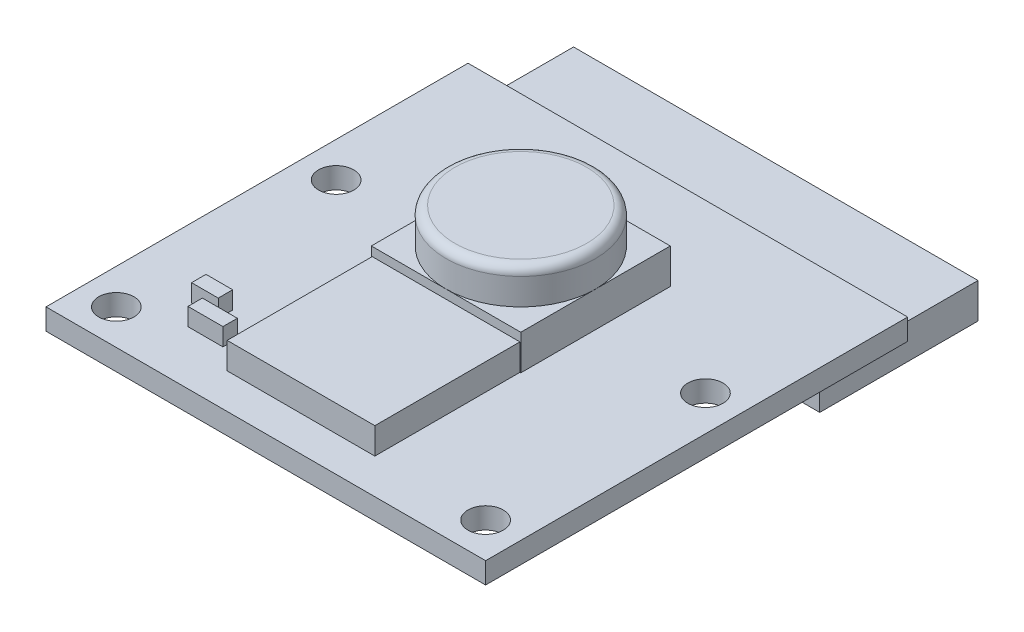
SolidWorks part; units mm, degrees
ref_plane "Front Plane" through (0, 0, 0) normal (0, 0, 1) x (1, 0, 0)
ref_plane "Top Plane" through (0, 0, 0) normal (0, 1, 0) x (1, 0, 0)
ref_plane "Right Plane" through (0, 0, 0) normal (1, 0, 0) x (0, 0, -1)
sketch "Sketch1" plane through (0, 0, 0) normal (0, 1, 0) x (1, 0, 0)
  line L0 (2, 22) -> (23, 22) construction
  line L1 (0, 24) -> (25, 24)
  line L2 (0, 24) -> (0, 0)
  line L3 (0, 0) -> (25, 0)
  line L4 (25, 24) -> (25, 0)
  line L5 (8.25, 18.75) -> (16.75, 18.75)
  line L6 (8.25, 18.75) -> (8.25, 10.25)
  line L8 (16.75, 18.75) -> (16.75, 10.25)
  line L9 (23, 22) -> (23, 14.5) construction
  line L10 (23, 2) -> (2, 2) construction
  line L11 (23, 14.5) -> (23, 2) construction
  line L12 (2, 2) -> (2, 14.5) construction
  line L13 (12.5, 14.5) -> (23, 14.5) construction
  line L14 (0, 24) -> (1, 29) construction
  line L17 (8.3, 2) -> (16.7, 2)
  line L19 (1, 29) -> (24, 29)
  line L20 (1, 29) -> (1, 20)
  line L21 (1, 20) -> (24, 20)
  line L22 (24, 29) -> (24, 20)
  line L23 (24, 29) -> (25, 24) construction
  line L24 (8.25, 10.25) -> (16.75, 10.25)
  line L25 (8.3, 2) -> (8.3, 10.25)
  line L26 (16.7, 2) -> (16.7, 10.25)
  line L27 (8.25, 10.25) -> (8.3, 2) construction
  line L28 (16.75, 10.25) -> (16.7, 2) construction
  line L30 (3.9479, 5.1506) -> (5.4647, 5.1506)
  line L31 (3.9479, 5.1506) -> (3.9479, 4.3307)
  line L32 (3.9479, 4.3307) -> (5.4647, 4.3307)
  line L33 (5.4647, 5.1506) -> (5.4647, 4.3307)
  line L34 (5.0137, 3.8797) -> (7.002, 3.8797)
  line L35 (5.0137, 3.8797) -> (5.0137, 3.0598)
  line L36 (5.0137, 3.0598) -> (7.002, 3.0598)
  line L37 (7.002, 3.8797) -> (7.002, 3.0598)
  circle A0 centre (2, 22) radius 1 construction
  circle A1 centre (2, 2) radius 1
  circle A2 centre (23, 22) radius 1 construction
  circle A3 centre (23, 2) radius 1
  circle A4 centre (2, 14.5) radius 1
  circle A5 centre (23, 14.5) radius 1
  circle A6 centre (12.5, 14.5) radius 4.25
  dimension "D1" = 2
  dimension "D8" = 14.5
  dimension "D10" = 8.5
  dimension "D2" = 25
  dimension "D3" = 24
  dimension "D4" = 20
  dimension "D5" = 21
  dimension "D6" = 2
  dimension "D7" = 2
  dimension "D9" = 12.5
  dimension "D11" = 23
  dimension "D12" = 4
  dimension "D13" = 5
  dimension "D14" = 8.4
extrude "Boss-Extrude1" add sketch "Sketch1" along normal blind 1.2 contours L1 L22 L21 L20 L2 L3 L4 A5 A4 A3 A2 A1 A0 L8 L17 L6 L5 | L24 L17 | A6 L8 | A6 L8 L5 | A6 L5 L6 | A6 | A6 L6 L24 | L22 L1 L20 L21 | L33 L30 L31 L32 | L37 L34 L35 L36 region at (0.5, 0, -23.6534) region at (12.5, 0, -22) region at (9.1993, 0, -17.8007) region at (15.8007, 0, -17.8007) region at (12.5, 0, -14.5) region at (9.1993, 0, -11.1993) region at (15.8007, 0, -11.1993) region at (12.5, 0, -6.125) region at (4.7063, 0, -4.7406) region at (6.0079, 0, -3.4698)
extrude "Boss-Extrude2" add sketch "Sketch1<3>" along normal blind 1.5 from surface contours L24 L17 region at (12.5, 0, -6.125) starting at face at (12.5, 1.2, -12)
sketch "Sketch1<3>" plane through (0, 0, 0) normal (0, 1, 0) x (1, 0, 0) same geometry as "Sketch1"
extrude "Boss-Extrude3" add sketch "Sketch1<4>" along normal blind 2 from surface contours A6 L8 | A6 L6 L24 | A6 L5 L6 | A6 L8 L5 | A6 region at (9.1993, 0, -17.8007) region at (15.8007, 0, -17.8007) region at (12.5, 0, -14.5) region at (9.1993, 0, -11.1993) region at (15.8007, 0, -11.1993) starting at face at (12.5, 1.2, -6.125)
sketch "Sketch1<4>" plane through (0, 0, 0) normal (0, 1, 0) x (1, 0, 0) same geometry as "Sketch1"
extrude "Boss-Extrude4" add sketch "Sketch1<5>" along normal blind 1 from surface contours L33 L30 L31 L32 | L37 L34 L35 L36 region at (4.7063, 0, -4.7406) region at (6.0079, 0, -3.4698) starting at face at (12.5, 1.2, -10.3125)
sketch "Sketch1<5>" plane through (0, 0, 0) normal (0, 1, 0) x (1, 0, 0) same geometry as "Sketch1"
extrude "Boss-Extrude5" add sketch "Sketch1<6>" against normal blind 2 contours L22 L1 L20 L21 | L22 L19 L20 L1 region at (12.5, 0, -26.5) region at (12.5, 0, -22)
sketch "Sketch1<6>" plane through (0, 0, 0) normal (0, 1, 0) x (1, 0, 0) same geometry as "Sketch1"
extrude "Boss-Extrude6" add sketch "Sketch1<7>" along normal blind 2 from surface contours A6 region at (12.5, 0, -14.5) starting at face at (12.5, 3.2, -14.5)
sketch "Sketch1<7>" plane through (0, 0, 0) normal (0, 1, 0) x (1, 0, 0) same geometry as "Sketch1"
fillet "Fillet1" radius 0.5 1 edges at (12.5, 5.2, -18.75)
